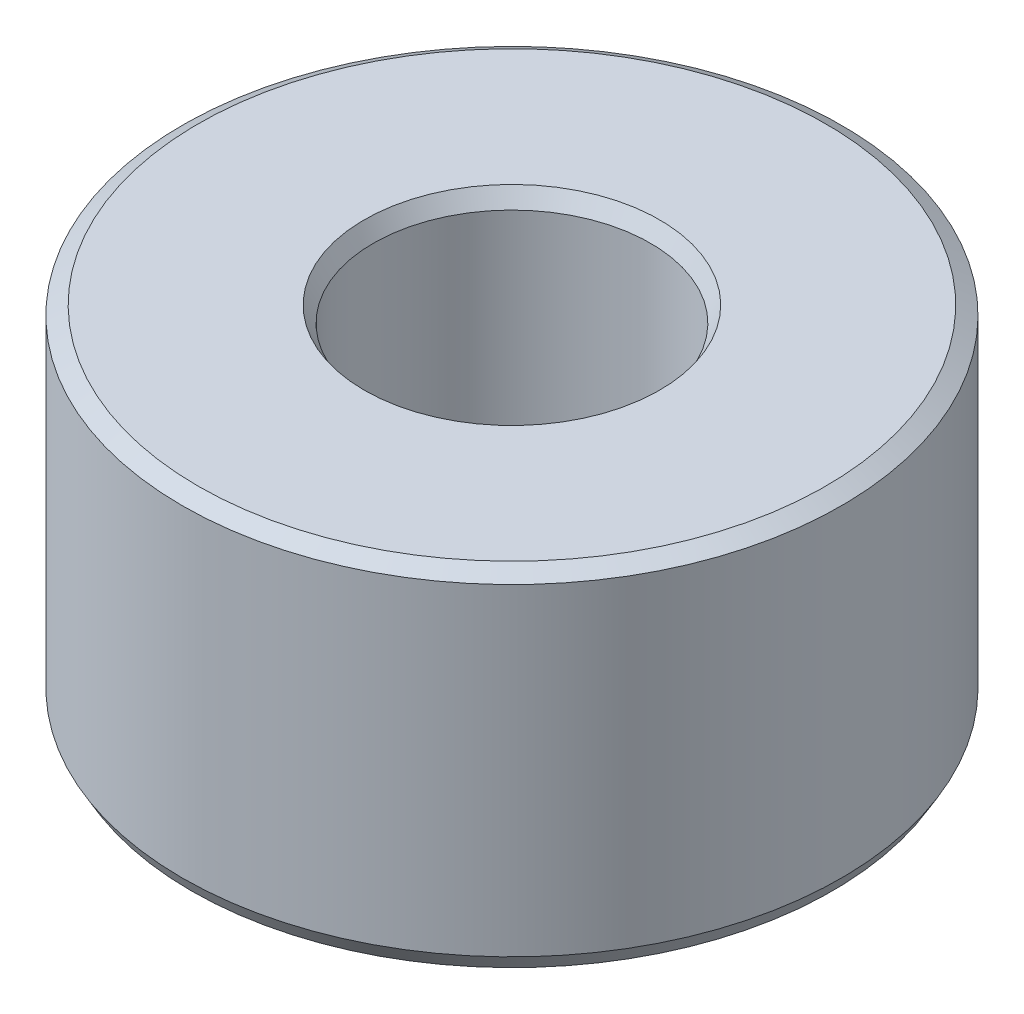
SolidWorks part; units mm, degrees
ref_plane "Front Plane" through (0, 0, 0) normal (0, 0, 1) x (1, 0, 0)
ref_plane "Top Plane" through (0, 0, 0) normal (0, 1, 0) x (1, 0, 0)
ref_plane "Right Plane" through (0, 0, 0) normal (1, 0, 0) x (0, 0, -1)
sketch "Sketch1" plane through (0, 0, 0) normal (0, 1, 0) x (1, 0, 0)
  circle A0 centre (0, 0) radius 55
  dimension "SLEEVE_OD" = 110
extrude "Boss-Extrude1" add sketch "Sketch1" along normal blind 57.9522
sketch "Sketch2" plane through (0, 0, 0) normal (0, 1, 0) x (1, 0, 0)
  circle A0 centre (0, 0) radius 23.1244
  dimension "BORE_D" = 46.2488
extrude "Cut-Extrude1" cut sketch "Sketch2" along normal through all
chamfer "Chamfer1" distance 1.5178 angle 60 4 edges at (0, 57.9522, 23.1244) (0, 0, 23.1244) (0, 0, 55) (0, 57.9522, 55) first distance on face at (0, 57.9522, 23.1244) first distance on face at (0, 0, 23.1244) first distance on face at (0, 57.9522, 55)
